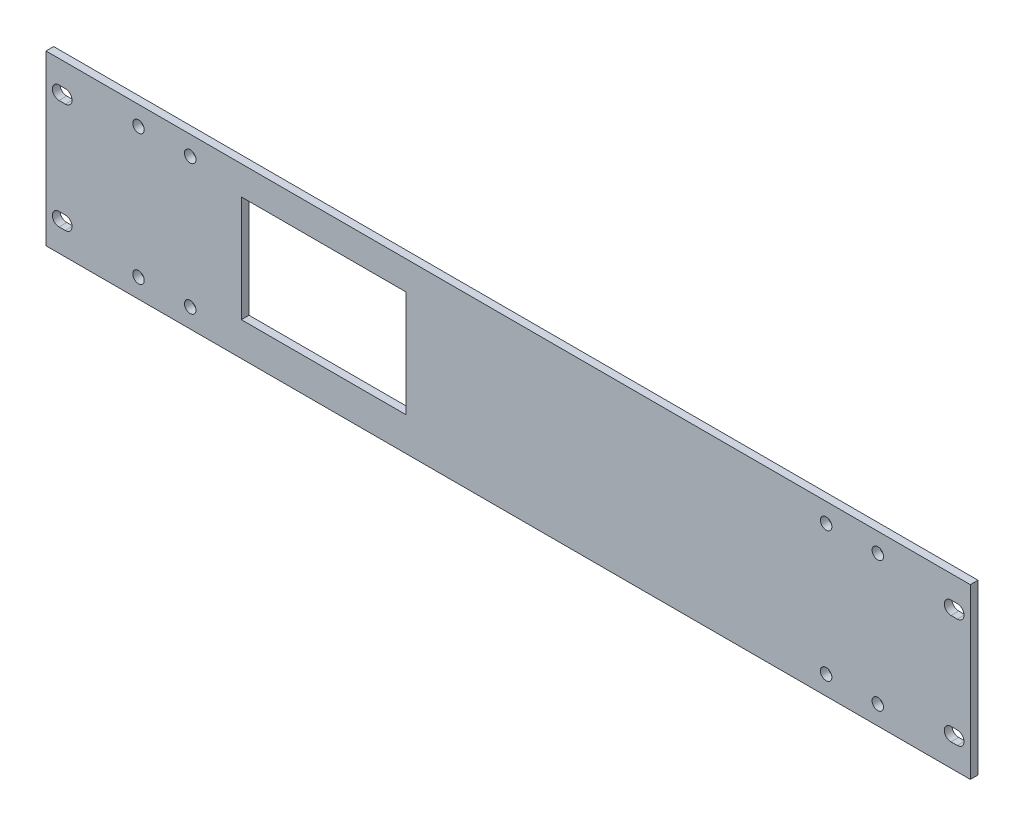
SolidWorks part; units mm, degrees
material "1060 Сплав"
ref_plane "Front" through (0, 0, 0) normal (0, 0, 1) x (1, 0, 0)
ref_plane "Top" through (0, 0, 0) normal (0, 1, 0) x (1, 0, 0)
ref_plane "Right" through (0, 0, 0) normal (1, 0, 0) x (0, 0, -1)
sketch "Эскиз1" plane through (0, 0, 0) normal (0, 0, 1) x (1, 0, 0)
  line L1 (0, 0) -> (482.6, 0)
  line L2 (0, 0) -> (0, 88.1)
  line L3 (0, 88.1) -> (482.6, 88.1)
  line L4 (482.6, 0) -> (482.6, 88.1)
  dimension "D1" = 88.1
  dimension "D2" = 482.6
extrude "Бобышка-Вытянуть1" add sketch "Эскиз1" along normal blind 4
sketch "Эскиз2" plane through (0, 0, 4) normal (0, 0, 1) x (1, 0, 0)
  line L0 (6.8, 72.62) -> (10.1, 72.62) construction
  line L1 (6.8, 76.12) -> (10.1, 76.12)
  line L2 (6.8, 69.12) -> (10.1, 69.12)
  line L3 (0, 88.1) -> (0, 0) construction
  line L4 (482.6, 88.1) -> (0, 88.1) construction
  line L5 (472.5, 72.62) -> (475.8, 72.62) construction
  line L6 (472.5, 76.12) -> (475.8, 76.12)
  line L7 (472.5, 69.12) -> (475.8, 69.12)
  line L8 (472.5, 15.47) -> (475.8, 15.47) construction
  line L9 (472.5, 18.97) -> (475.8, 18.97)
  line L10 (472.5, 11.97) -> (475.8, 11.97)
  line L11 (6.8, 15.47) -> (10.1, 15.47) construction
  line L12 (6.8, 18.97) -> (10.1, 18.97)
  line L13 (6.8, 11.97) -> (10.1, 11.97)
  line L15 (482.6, 0) -> (482.6, 88.1) construction
  arc A0 (6.8, 76.12) -> (6.8, 69.12) centre (6.8, 72.62) ccw
  arc A1 (10.1, 69.12) -> (10.1, 76.12) centre (10.1, 72.62) ccw
  arc A2 (472.5, 76.12) -> (472.5, 69.12) centre (472.5, 72.62) ccw
  arc A3 (475.8, 69.12) -> (475.8, 76.12) centre (475.8, 72.62) ccw
  arc A4 (472.5, 18.97) -> (472.5, 11.97) centre (472.5, 15.47) ccw
  arc A5 (475.8, 11.97) -> (475.8, 18.97) centre (475.8, 15.47) ccw
  arc A6 (6.8, 18.97) -> (6.8, 11.97) centre (6.8, 15.47) ccw
  arc A7 (10.1, 11.97) -> (10.1, 18.97) centre (10.1, 15.47) ccw
  point P2 (8.45, 72.62)
  point P16 (474.15, 72.62)
  point P23 (474.15, 15.47)
  point P30 (8.45, 15.47)
  dimension "D2" = 3.5
  dimension "D4" = 15.48
  dimension "D7" = 6.8
  dimension "D1" = 3.3
  dimension "D3" = 6.8
  dimension "D5" = 2
  dimension "D6" = 2
extrude "Вырез-Вытянуть1" cut sketch "Эскиз2" against normal through all
sketch "Эскиз3" plane through (0, 0, 4) normal (0, 0, 1) x (1, 0, 0)
  line L0 (0, 88.1) -> (0, 0) construction
  line L1 (482.6, 88.1) -> (0, 88.1) construction
  line L2 (0, 0) -> (482.6, 0) construction
  line L3 (482.6, 0) -> (482.6, 88.1) construction
  circle A0 centre (48.3, 78.1) radius 3
  circle A1 centre (434.3, 78.1) radius 3
  circle A2 centre (434.3, 10) radius 3
  circle A3 centre (48.3, 10) radius 3
  circle A4 centre (75.3, 78.1) radius 3
  circle A5 centre (407.3, 78.1) radius 3
  circle A6 centre (407.3, 10) radius 3
  circle A7 centre (75.3, 10) radius 3
  dimension "D1" = 6
  dimension "D2" = 48.3
  dimension "D3" = 10
  dimension "D6" = 10
  dimension "D7" = 48.3
  dimension "D8" = 6
  dimension "D9" = 27
  dimension "D10" = 10
  dimension "D13" = 27
  dimension "D4" = 2
  dimension "D5" = 2
  dimension "D11" = 2
  dimension "D12" = 2
extrude "Вырез-Вытянуть2" cut sketch "Эскиз3" against normal through all
sketch "Эскиз4" plane through (0, 0, 4) normal (0, 0, 1) x (1, 0, 0)
  line L0 (0, 88.1) -> (0, 0) construction
  line L1 (102, 73.1) -> (188, 73.1)
  line L2 (102, 73.1) -> (102, 17.6)
  line L3 (102, 17.6) -> (188, 17.6)
  line L4 (188, 73.1) -> (188, 17.6)
  line L5 (482.6, 88.1) -> (0, 88.1) construction
  dimension "D1" = 55.5
  dimension "D2" = 86
  dimension "D3" = 102
  dimension "D4" = 15
extrude "Вырез-Вытянуть3" cut sketch "Эскиз4" against normal through all
